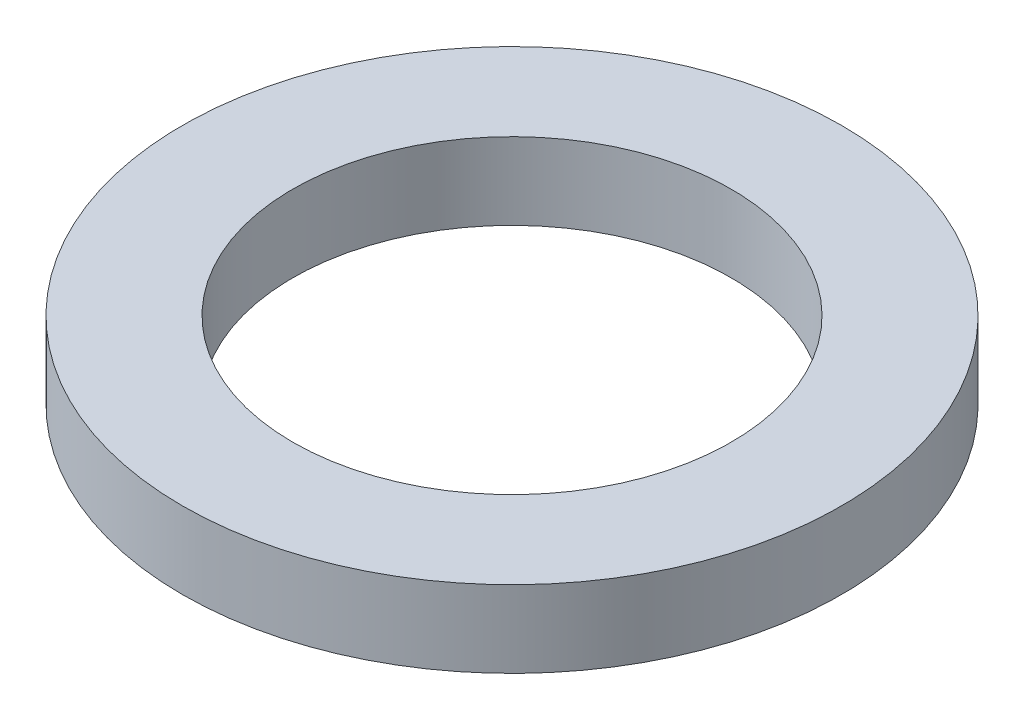
SolidWorks part; units mm, degrees
material "6061-T6 (SS)"
ref_plane "Front Plane" through (0, 0, 0) normal (0, 0, 1) x (1, 0, 0)
ref_plane "Top Plane" through (0, 0, 0) normal (0, 1, 0) x (1, 0, 0)
ref_plane "Right Plane" through (0, 0, 0) normal (1, 0, 0) x (0, 0, -1)
sketch "Sketch1" plane through (0, 0, 0) normal (0, 0, 1) x (1, 0, 0)
  line L0 (0, 22.7096) -> (0, -29.6046) construction
  line L2 (27.178, -9.525) -> (40.8559, -9.525)
  line L3 (27.178, -9.525) -> (27.178, 0)
  line L4 (27.178, 0) -> (40.8559, 0)
  line L5 (40.8559, -9.525) -> (40.8559, 0)
  dimension "D1" = 81.7118
  dimension "D2" = 9.525
  dimension "D3" = 54.356
revolve "Revolve1" add sketch "Sketch1" angle 360 about L0
ref_axis "Axis1" through (0, -10.0013, 0) along (0, 1, 0)
